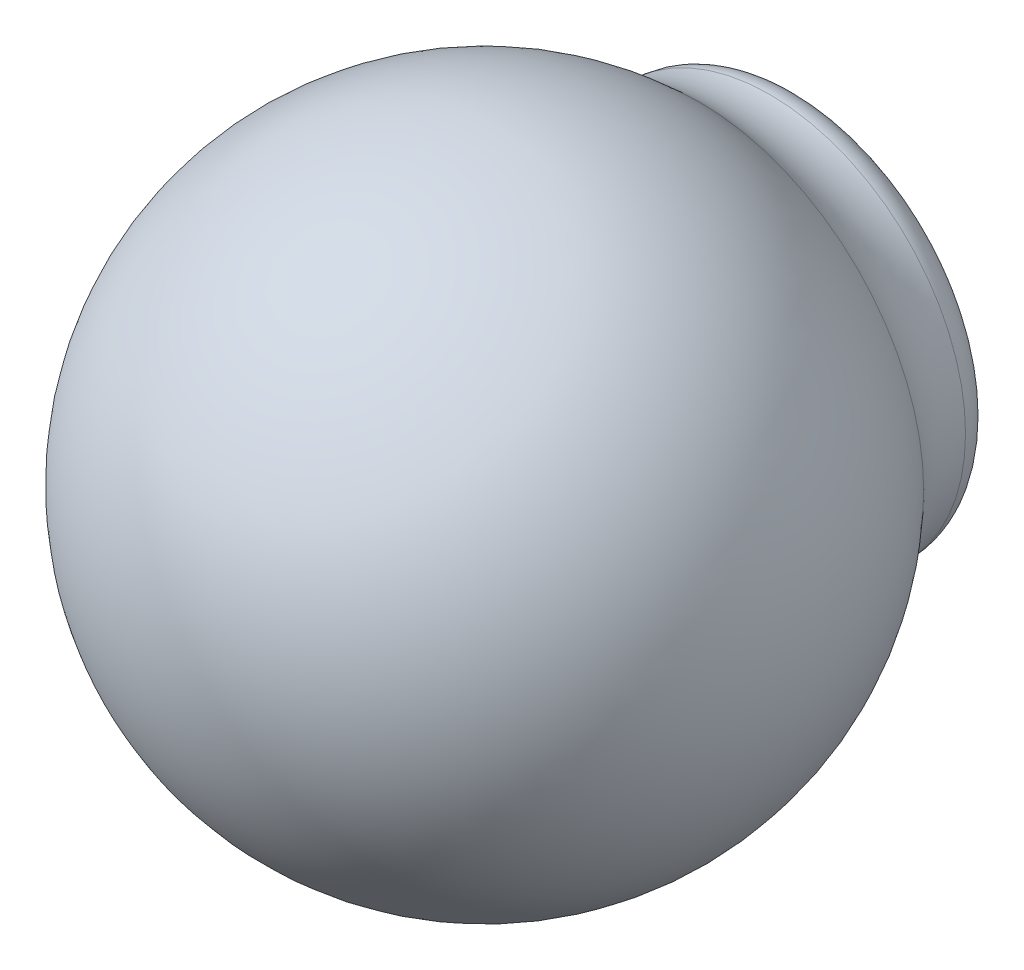
SolidWorks part; units mm, degrees
ref_plane "Front Plane" through (0, 0, 0) normal (0, 0, 1) x (1, 0, 0)
ref_plane "Top Plane" through (0, 0, 0) normal (0, 1, 0) x (1, 0, 0)
ref_plane "Right Plane" through (0, 0, 0) normal (1, 0, 0) x (0, 0, -1)
sketch "Sketch2" plane through (0, 0, 0) normal (0, 0, 1) x (1, 0, 0)
  circle A2 centre (0, 11.2528) radius 3.4
  circle A3 centre (0, 11.2528) radius 3.4
  circle A17 centre (11.2528, 0) radius 3.4
  circle A18 centre (11.2528, 0) radius 3.4
  circle A20 centre (0, -11.2528) radius 3.4
  circle A21 centre (0, -11.2528) radius 3.4
  circle A22 centre (0, 0) radius 18.9215
  circle A23 centre (-11.2528, 0) radius 3.4
  circle A24 centre (-11.2528, 0) radius 3.4
  dimension "D1" = 0.4
  dimension "D2" = 0.4
  dimension "D3" = 0.4
  dimension "D4" = 0.4
extrude "Boss-Extrude1" add sketch "Sketch2" along normal blind 10
fillet "Fillet1" radius 3 1 edges at (18.9215, 0, 0)
sketch "Sketch3" plane through (0, 0, 10) normal (0, 0, 1) x (1, 0, 0)
  circle A0 centre (0, 11.2528) radius 3.4 construction
  circle A1 centre (0, 0) radius 18.9215
  circle A2 centre (0, 0) radius 18.9215
  circle A3 centre (0, 11.2528) radius 3.4
  circle A4 centre (11.2528, 0) radius 3.4 construction
  circle A5 centre (11.2528, 0) radius 3.4
  circle A6 centre (-11.2528, 0) radius 3.4 construction
  circle A7 centre (-11.2528, 0) radius 3.4
  circle A8 centre (0, -11.2528) radius 3.4 construction
  circle A9 centre (0, -11.2528) radius 3.4
  dimension "D1" = 0
extrude "Boss-Extrude2" add sketch "Sketch3" along normal blind 0.5
sketch "Sketch4" plane through (0, 0, 10.5) normal (0, 0, 1) x (1, 0, 0)
  circle A1 centre (0, 0) radius 18.9215
  circle A2 centre (0, 0) radius 18.9215
  dimension "D1" = 0
extrude "Boss-Extrude3" add sketch "Sketch4" along normal blind 5
sketch "Sketch8" plane through (0, 0, 15.5) normal (0, 0, 1) x (1, 0, 0)
  circle A1 centre (0, 0) radius 18.9215
  circle A2 centre (0, 0) radius 18.9215
  dimension "D1" = 0
extrude "Boss-Extrude4" add sketch "Sketch8" along normal blind 15
sketch "Sketch9" plane through (0, 0, 30.5) normal (0, 0, 1) x (1, 0, 0)
  line L2 (0, 0) -> (0, 30)
  line L3 (0, 30) -> (0, -30)
  arc A0 (0, -30) -> (0, 30) centre (0, 0) ccw
  dimension "D1" = 60
revolve "Revolve2" add sketch "Sketch9" angle 360 about L2 region at (8.0305, 0, 30.5) region at (0.6708, 24.4608, 30.5)
sketch "Sketch10" plane through (0, 0, 0) normal (0, 0, -1) x (-1, 0, 0)
  circle A0 centre (0, 0) radius 4.25
  dimension "D1" = 8.5
extrude "Cut-Extrude2" cut sketch "Sketch10" against normal blind 40
fillet "Fillet2" radius 10 1 edges at (18.9215, 0, 7.2196)
sketch "Sketch11" plane through (0, 0, 0) normal (0, 0, -1) x (-1, 0, 0)
  circle A0 centre (0, -11.2528) radius 3.4
  circle A1 centre (-11.2528, 0) radius 3.4
  circle A2 centre (0, 11.2528) radius 3.4
  circle A3 centre (11.2528, 0) radius 3.4
extrude "Cut-Extrude3" cut sketch "Sketch11" against normal blind 10.5
